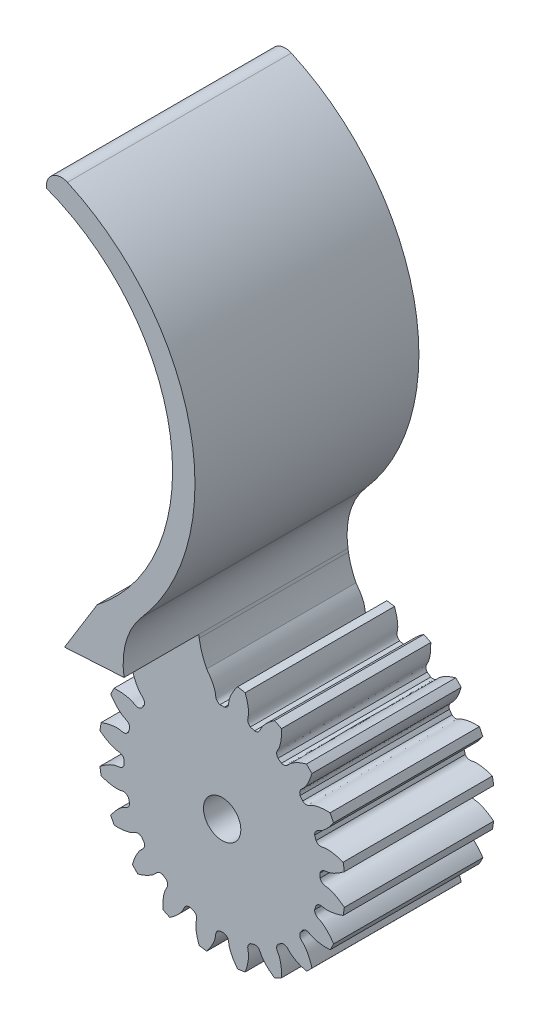
SolidWorks part; units mm, degrees
material "聚脂树脂"
ref_plane "前视基准面" through (0, 0, 0) normal (0, 0, 1) x (1, 0, 0)
ref_plane "上视基准面" through (0, 0, 0) normal (0, 1, 0) x (1, 0, 0)
ref_plane "右视基准面" through (0, 0, 0) normal (1, 0, 0) x (0, 0, -1)
other "Configuration Table"
sketch "草图1" plane through (0, 0, 0) normal (0, 0, 1) x (1, 0, 0)
  circle A0 centre (0, 0) radius 16.5
extrude "凸台-拉伸1" add sketch "草图1" along normal blind 20
ref_axis "基准轴1" through (0, 0, -1.5) along (0, 0, 1)
sketch "草图2" plane through (0, 0, 0) normal (0, 0, 1) x (1, 0, 0)
  line L0 (0, 0) -> (0, 16.5) construction
  circle A0 centre (0, 0) radius 16.5 construction
  arc A1 (0.29, 13.1218) -> (-0.29, 13.1218) centre (0, 0) ccw
  arc A2 (4.7717, 18.7474) -> (-4.7717, 18.7474) centre (0, 0) ccw
  spline S0 degree 3 poles (0.29, 13.1218) (0.9168, 13.3402) (0.8356, 13.7807) (0.9193, 14.205) (0.9283, 14.2463) (0.9395, 14.293) (0.9529, 14.3448) (0.969, 14.4018) (0.9878, 14.4638) (1.0095, 14.5309) (1.0345, 14.6028) (1.0629, 14.6795) (1.0948, 14.7608) (1.1305, 14.8467) (1.1702, 14.9371) (1.2141, 15.0317) (1.2623, 15.1305) (1.315, 15.2334) (1.3725, 15.3401) (1.4349, 15.4506) (1.5023, 15.5646) (1.575, 15.6821) (1.653, 15.8029) (1.7366, 15.9267) (1.826, 16.0534) (1.9211, 16.1829) (2.0223, 16.3149) (2.1296, 16.4493) (2.2432, 16.5859) (2.3632, 16.7244) (2.4897, 16.8646) (2.6229, 17.0065) (2.7628, 17.1496) (2.9095, 17.2939) (3.0632, 17.4391) (3.224, 17.585) (3.3918, 17.7313) (3.567, 17.8779) (3.7493, 18.0245) (3.9391, 18.1709) (4.1363, 18.3167) (4.4122, 18.5125) (4.6259, 18.6545) (4.7717, 18.7474) knots 0 0 0 0 0.165916 0.170906 0.176664 0.183189 0.190482 0.198542 0.207371 0.216967 0.22733 0.238462 0.250361 0.263027 0.276462 0.290664 0.305634 0.321371 0.337876 0.355149 0.37319 0.391998 0.411574 0.431917 0.453028 0.474907 0.497554 0.520968 0.54515 0.570099 0.595817 0.622302 0.649554 0.677575 0.706363 0.735918 0.766242 0.797333 0.829191 0.861818 0.895212 0.929373 1 1 1 1
  spline S1 degree 3 poles (-0.29, 13.1218) (-0.9168, 13.3402) (-0.8356, 13.7807) (-0.9193, 14.205) (-0.9283, 14.2463) (-0.9395, 14.293) (-0.9529, 14.3448) (-0.969, 14.4018) (-0.9878, 14.4638) (-1.0095, 14.5309) (-1.0345, 14.6028) (-1.0629, 14.6795) (-1.0948, 14.7608) (-1.1305, 14.8467) (-1.1702, 14.9371) (-1.2141, 15.0317) (-1.2623, 15.1305) (-1.315, 15.2334) (-1.3725, 15.3401) (-1.4349, 15.4506) (-1.5023, 15.5646) (-1.575, 15.6821) (-1.653, 15.8029) (-1.7366, 15.9267) (-1.826, 16.0534) (-1.9211, 16.1829) (-2.0223, 16.3149) (-2.1296, 16.4493) (-2.2432, 16.5859) (-2.3632, 16.7244) (-2.4897, 16.8646) (-2.6229, 17.0065) (-2.7628, 17.1496) (-2.9095, 17.2939) (-3.0632, 17.4391) (-3.224, 17.585) (-3.3918, 17.7313) (-3.567, 17.8779) (-3.7493, 18.0245) (-3.9391, 18.1709) (-4.1363, 18.3167) (-4.4122, 18.5125) (-4.6259, 18.6545) (-4.7717, 18.7474) knots 0 0 0 0 0.165916 0.170906 0.176664 0.183189 0.190482 0.198542 0.207371 0.216967 0.22733 0.238462 0.250361 0.263027 0.276462 0.290664 0.305634 0.321371 0.337876 0.355149 0.37319 0.391998 0.411574 0.431917 0.453028 0.474907 0.497554 0.520968 0.54515 0.570099 0.595817 0.622302 0.649554 0.677575 0.706363 0.735918 0.766242 0.797333 0.829191 0.861818 0.895212 0.929373 1 1 1 1
extrude "切除-拉伸1" cut sketch "草图2" along normal through all
pattern_circular "阵列(圆周)1" count 20 over 360 about axis through (0, 0, -1.5) along (0, 0, 1) of "切除-拉伸1"
sketch "草图3" plane through (0, 0, 0) normal (0, 0, 1) x (1, 0, 0)
  circle A0 centre (0, 0) radius 15 construction
  dimension "Dn" = 30
sketch "草图4" plane through (0, 0, 20) normal (0, 0, 1) x (1, 0, 0)
  line L0 (0, 0) -> (0, 24.252) construction
  line L1 (0, 0) -> (-4.1504, 26.2048) construction
  line L2 (-14.6667, -3.2847) -> (-22.6322, 47.0071) construction
  line L3 (-2.5812, 16.2969) -> (-3.9432, 24.8963)
  line L4 (-9.8663, 11.4731) -> (-11.763, 23.4486)
  line L5 (-16.5467, 75.4159) -> (-13.5328, 71.4159)
  line L6 (-11.294, 12.029) -> (-10.4295, 15.029)
  line L7 (-3.0932, 16.2075) -> (-2.5812, 16.2969)
  line L8 (0, 0) -> (-34.8237, -5.5155) construction
  arc A2 (-2.0665, 16.3701) -> (-3.0932, 16.2075) centre (0, 0) ccw construction
  circle A4 centre (-22.6411, 47.0635) radius 26 construction
  circle A5 centre (-22.6411, 47.0635) radius 29 construction
  arc A6 (-11.763, 23.4486) -> (-13.5328, 71.4159) centre (-22.6411, 47.0635) ccw
  arc A7 (-3.9432, 24.8963) -> (-16.5467, 75.4159) centre (-22.6411, 47.0635) ccw
  arc A8 (-3.7791, 12.5692) -> (-4.3306, 12.39) centre (0, 0) ccw construction
  arc A9 (-7.024, 14.9303) -> (-7.9502, 14.4584) centre (0, 0) ccw construction
  arc A10 (-7.4782, 10.7862) -> (-7.9474, 10.4453) centre (0, 0) ccw construction
  arc A12 (-3.7791, 12.5692) -> (-4.3306, 12.39) centre (0, 0) ccw
  arc A13 (-7.024, 14.9303) -> (-7.9502, 14.4584) centre (0, 0) ccw
  arc A14 (-7.4782, 10.7862) -> (-7.9474, 10.4453) centre (0, 0) ccw
  spline S0 degree 3 poles (1533.8481, 1281.675) (-100.0743, -100.0538) (-37.3462, 19.765) (-11.0168, 11.9483) (-10.7713, 11.8675) (-10.4966, 11.7648) (-10.2471, 11.6599) (-10.0224, 11.5547) (-9.822, 11.4509) (-9.671, 11.3649) (-9.5386, 11.2841) (-9.4441, 11.2225) (-9.3578, 11.1623) (-9.3008, 11.1209) (-9.2491, 11.0817) (-9.2026, 11.0451) (-9.1503, 11.0021) (-9.105, 10.9626) (-5.12, 7.2674) (-20.1054, -16.3486) (1244.1384, 1569.7336) knots -10.650201 -10.650201 -10.650201 -10.650201 0.502446 0.525093 0.568083 0.608002 0.644851 0.678629 0.709336 0.736973 0.749639 0.77267 0.783033 0.792629 0.801458 0.809518 0.816811 0.829094 0.834084 3.036535 3.036535 3.036535 3.036535 only from (-11.294, 12.029) to (-7.9474, 10.4453) construction
  spline S1 degree 3 poles (-2001.2932, -83.8658) (25.0446, 6.6561) (-2.87, 8.4138) (-3.5171, 13.8097) (-3.5224, 13.8696) (-3.5265, 13.9372) (-3.5289, 13.9963) (-3.5307, 14.0865) (-3.5293, 14.2134) (-3.5206, 14.3824) (-3.5033, 14.5733) (-3.4754, 14.7858) (-3.4352, 15.0192) (-3.381, 15.2729) (-3.3111, 15.5461) (-3.2398, 15.7847) (-3.1737, 15.9845) (5.9613, 41.8314) (139.7678, 22.1516) (-1938.4783, -487.5615) knots -2.036559 -2.036559 -2.036559 -2.036559 0.165916 0.170906 0.183189 0.190482 0.198542 0.207371 0.22733 0.250361 0.276462 0.305634 0.337876 0.37319 0.411574 0.453028 0.474907 0.497554 11.650216 11.650216 11.650216 11.650216 only from (-3.7791, 12.5692) to (-3.0932, 16.2075) construction
  spline S2 degree 3 poles (1854.8356, 744.9602) (-126.0947, -64.2322) (-29.4106, 30.3383) (-6.7853, 14.7679) (-6.5768, 14.6152) (-6.3474, 14.4326) (-6.1425, 14.2557) (-5.9612, 14.0862) (-5.8028, 13.9257) (-5.6857, 13.7971) (-5.5848, 13.6794) (-5.514, 13.5916) (-5.4504, 13.5077) (-5.409, 13.4507) (-5.3719, 13.3975) (-5.3391, 13.3482) (-5.3027, 13.2912) (-5.2717, 13.2396) (-2.6237, 8.4939) (-24.1734, -9.3355) (1668.3203, 1108.4455) knots -10.650201 -10.650201 -10.650201 -10.650201 0.502446 0.525093 0.568083 0.608002 0.644851 0.678629 0.709336 0.736973 0.749639 0.77267 0.783033 0.792629 0.801458 0.809518 0.816811 0.829094 0.834084 3.036535 3.036535 3.036535 3.036535 only from (-7.024, 14.9303) to (-4.3306, 12.39) construction
  spline S3 degree 3 poles (-1877.4269, -698.1947) (21.762, 14.0695) (-5.3295, 7.1151) (-7.6124, 12.047) (-7.636, 12.1023) (-7.6607, 12.1653) (-7.6812, 12.2208) (-7.7108, 12.3061) (-7.7487, 12.4272) (-7.7927, 12.5905) (-7.8352, 12.7775) (-7.8743, 12.9882) (-7.9082, 13.2226) (-7.9351, 13.4806) (-7.9531, 13.762) (-7.959, 14.011) (-7.9578, 14.2215) (-7.257, 41.6261) (126.0819, 64.2581) (-1692.9376, -1062.7213) knots -2.036559 -2.036559 -2.036559 -2.036559 0.165916 0.170906 0.183189 0.190482 0.198542 0.207371 0.22733 0.250361 0.276462 0.305634 0.337876 0.37319 0.411574 0.453028 0.474907 0.497554 11.650216 11.650216 11.650216 11.650216 only from (-7.4782, 10.7862) to (-7.9502, 14.4584) construction
  spline S4 degree 3 poles (-3.7791, 12.5692) (-3.2504, 12.9706) (-3.4637, 13.3644) (-3.5171, 13.8097) (-3.5224, 13.8696) (-3.5265, 13.9372) (-3.5289, 13.9963) (-3.5307, 14.0865) (-3.5293, 14.2134) (-3.5206, 14.3824) (-3.5033, 14.5733) (-3.4754, 14.7858) (-3.4352, 15.0192) (-3.381, 15.2729) (-3.3111, 15.5461) (-3.224, 15.8378) (-3.1479, 16.0599) (-3.1017, 16.1848) (-3.0932, 16.2075) knots 0 0 0 0 0.165916 0.170906 0.183189 0.190482 0.198542 0.207371 0.22733 0.250361 0.276462 0.305634 0.337876 0.37319 0.411574 0.453028 0.497554 0.507432 0.507432 0.507432 0.507432
  spline S5 degree 3 poles (-7.024, 14.9303) (-6.9129, 14.8568) (-6.7202, 14.7228) (-6.459, 14.5233) (-6.2419, 14.3433) (-6.0489, 14.1699) (-5.8792, 14.0047) (-5.7318, 13.8492) (-5.6234, 13.7255) (-5.5309, 13.613) (-5.4664, 13.5298) (-5.409, 13.4507) (-5.3719, 13.3975) (-5.3391, 13.3482) (-5.3027, 13.2912) (-5.2717, 13.2396) (-5.0532, 12.848) (-4.9943, 12.404) (-4.3306, 12.39) knots 0.492568 0.492568 0.492568 0.492568 0.546972 0.588426 0.62681 0.662124 0.694366 0.723538 0.749639 0.761538 0.783033 0.792629 0.801458 0.809518 0.816811 0.829094 0.834084 1 1 1 1
  spline S6 degree 3 poles (-7.4782, 10.7862) (-7.0995, 11.3313) (-7.424, 11.64) (-7.6124, 12.047) (-7.636, 12.1023) (-7.6607, 12.1653) (-7.6812, 12.2208) (-7.7108, 12.3061) (-7.7487, 12.4272) (-7.7927, 12.5905) (-7.8352, 12.7775) (-7.8743, 12.9882) (-7.9082, 13.2226) (-7.9351, 13.4806) (-7.9531, 13.762) (-7.9603, 14.0664) (-7.9566, 14.3011) (-7.9513, 14.4342) (-7.9502, 14.4584) knots 0 0 0 0 0.165916 0.170906 0.183189 0.190482 0.198542 0.207371 0.22733 0.250361 0.276462 0.305634 0.337876 0.37319 0.411574 0.453028 0.497554 0.507432 0.507432 0.507432 0.507432
  spline S7 degree 3 poles (-11.294, 12.029) (-11.1656, 11.9934) (-10.9409, 11.9255) (-10.6308, 11.8165) (-10.3687, 11.7125) (-10.1316, 11.6072) (-9.9192, 11.5025) (-9.7309, 11.4002) (-9.5896, 11.316) (-9.4669, 11.2376) (-9.3798, 11.1783) (-9.3008, 11.1209) (-9.2491, 11.0817) (-9.2026, 11.0451) (-9.1503, 11.0021) (-9.105, 10.9626) (-8.7761, 10.6576) (-8.5829, 10.2536) (-7.9474, 10.4453) knots 0.492568 0.492568 0.492568 0.492568 0.546972 0.588426 0.62681 0.662124 0.694366 0.723538 0.749639 0.761538 0.783033 0.792629 0.801458 0.809518 0.816811 0.829094 0.834084 1 1 1 1
  dimension "D6" = 52
  dimension "D7" = 48
  dimension "D5" = 58
  dimension "D1" = 9
  dimension "D2" = 15
  dimension "D3" = 7.95
  dimension "D4" = 25
  dimension "D8" = 4
  dimension "D9" = 3
extrude "凸台-拉伸2" add sketch "草图4" against normal blind 20 contours L4 S7 A14 S6 A13 S5 A12 S4 L7 L3 A7 L5 A6 | L6 S7 L4 region at (-2.9558, 16.9313, 20) region at (-10.5293, 12.8632, 20)
fillet "圆角1" radius 10 1 edges
fillet "圆角2" radius 2 1 edges at (-16.5467, 75.4159, 10)
fillet "圆角4" radius 10 1 edges at (-3.9432, 24.8963, 10)
sketch "草图5" plane through (0, 0, 20) normal (0, 0, 1) x (1, 0, 0)
  circle A0 centre (0, 0) radius 2.5
  dimension "D1" = 5
extrude "切除-拉伸2" cut sketch "草图5" against normal blind 20
chamfer "倒角1" distance 5 angle 45 1 edges at (-11.763, 23.4486, 10) first distance on face at (-11.0962, 19.2388, 10)
sketch "草图6" plane through (0, 0, 20) normal (0, 0, 1) x (1, 0, 0)
  line L1 (-6.7321, 26.4989) -> (-11.1191, 19.3832)
  line L2 (-11.1191, 19.3832) -> (-3.1432, 19.8453)
  arc A0 (-0.7983, 27.9876) -> (-10.7289, 73.504) centre (-22.6411, 47.0635) ccw construction
  arc A1 (-6.7321, 26.4989) -> (-13.5328, 71.4159) centre (-22.6411, 47.0635) ccw construction
  arc A2 (-10.7289, 73.504) -> (-13.5328, 71.4159) centre (-11.5504, 71.6805) ccw construction
  arc A3 (-0.7983, 27.9876) -> (-10.7289, 73.504) centre (-22.6411, 47.0635) ccw
  arc A4 (-6.7321, 26.4989) -> (-13.5328, 71.4159) centre (-22.6411, 47.0635) ccw
  arc A5 (-10.7289, 73.504) -> (-13.5328, 71.4159) centre (-11.5504, 71.6805) ccw
  arc A6 (-0.7983, 27.9876) -> (-3.1432, 19.8453) centre (6.7337, 21.4096) ccw construction
  arc A7 (-0.7983, 27.9876) -> (-3.1432, 19.8453) centre (6.7337, 21.4096) ccw
extrude "凸台-拉伸3" add sketch "草图6" along normal blind 10
